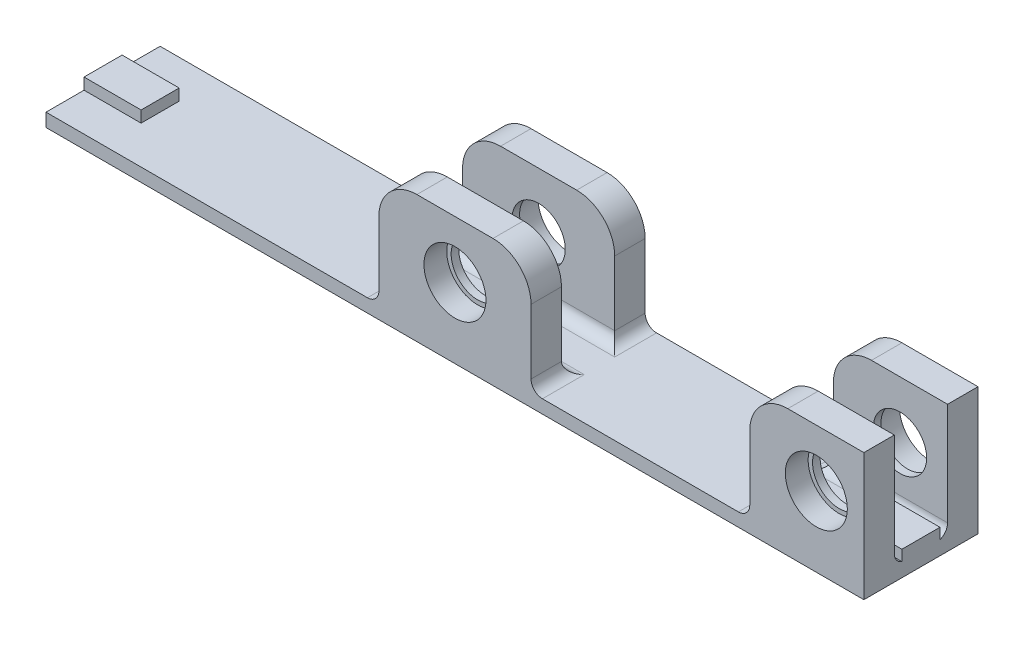
SolidWorks part; units mm, degrees
ref_plane "Front Plane" through (0, 0, 0) normal (0, 0, 1) x (1, 0, 0)
ref_plane "Top Plane" through (0, 0, 0) normal (0, 1, 0) x (1, 0, 0)
ref_plane "Right Plane" through (0, 0, 0) normal (1, 0, 0) x (0, 0, -1)
sketch "Sketch2" plane through (0, 0, 0) normal (0, 1, 0) x (1, 0, 0)
  line L1 (107.5, 15) -> (-107.5, 15)
  line L2 (107.5, 15) -> (107.5, -15)
  line L3 (107.5, -15) -> (-107.5, -15)
  line L4 (-107.5, 15) -> (-107.5, -15)
  line L5 (107.5, 15) -> (-107.5, -15) construction
  line L6 (107.5, -15) -> (-107.5, 15) construction
  point P0 (0, 0)
  dimension "D1" = 215
  dimension "D2" = 30
extrude "Boss-Extrude1" add sketch "Sketch2" along normal blind 3.5
sketch "HOLES TBD" plane through (0, 3.5, 0) normal (0, 1, 0) x (1, 0, 0)
  line L0 (100, 0) -> (-100, 0) construction
  circle A0 centre (-100, 0) radius 1.65
  circle A1 centre (100, 0) radius 1.65
  point P4 (0, 0)
  dimension "D2" = 3.3
  dimension "D1" = 200
sketch "Sketch4" plane through (0, 3.5, 0) normal (0, 1, 0) x (1, 0, 0)
  line L0 (-107.5, -15) -> (107.5, -15) construction
  line L1 (107.5, -15) -> (77.5, -15)
  line L2 (107.5, -15) -> (107.5, -7)
  line L3 (107.5, -7) -> (77.5, -7)
  line L4 (77.5, -15) -> (77.5, -7)
  line L5 (107.5, -15) -> (77.5, -7) construction
  line L6 (107.5, -7) -> (77.5, -15) construction
  line L7 (-20, -15) -> (20, -15)
  line L8 (-20, -15) -> (-20, -7)
  line L9 (-20, -7) -> (20, -7)
  line L10 (20, -15) -> (20, -7)
  line L11 (-20, -15) -> (20, -7) construction
  line L12 (-20, -7) -> (20, -15) construction
  line L13 (0, 0) -> (0, -15) construction
  line L14 (-100, 0) -> (100, 0) construction
  line L15 (-20, 7) -> (20, 15) construction
  line L16 (-20, 15) -> (20, 7) construction
  line L17 (107.5, 7) -> (77.5, 15) construction
  line L18 (107.5, 15) -> (77.5, 7) construction
  line L19 (20, 15) -> (20, 7)
  line L20 (-20, 7) -> (20, 7)
  line L21 (-20, 15) -> (-20, 7)
  line L22 (-20, 15) -> (20, 15)
  line L23 (77.5, 15) -> (77.5, 7)
  line L24 (107.5, 7) -> (77.5, 7)
  line L25 (107.5, 15) -> (107.5, 7)
  line L26 (107.5, 15) -> (77.5, 15)
  point P4 (92.5, -11)
  point P10 (0, -11)
  point P28 (0, 11)
  point P29 (92.5, 11)
  dimension "D1" = 8
  dimension "D2" = 30
  dimension "D3" = 40
extrude "Boss-Extrude2" add sketch "Sketch4" along normal blind 30
sketch "Sketch5" plane through (0, 0, 15) normal (0, 0, 1) x (1, 0, 0)
  line L0 (0, 3.5) -> (0, 18.5) construction
  line L3 (0, 18.5) -> (95, 18.5) construction
  line L6 (20, 33.5) -> (20, 3.5) construction
  circle A0 centre (0, 18.5) radius 8.15
  circle A1 centre (95, 18.5) radius 8.15
  point P10 (20, 18.5)
  dimension "D2" = 16.3
  dimension "D3" = 95
extrude "Bearing holes" cut sketch "Sketch5" against normal blind 6
mirror "Mirror1" about plane through (0, 0, 0) normal (0, 0, 1) of "Bearing holes"
sketch "Sketch7" plane through (0, 0, 9) normal (0, 0, 1) x (1, 0, 0)
  circle A0 centre (0, 18.5) radius 7
  circle A1 centre (95, 18.5) radius 7
  dimension "D1" = 14
extrude "Cut-Extrude2" cut sketch "Sketch7" against normal through all
chamfer "Chamfer1" [suppressed] distance 5 angle 45
fillet "Fillet1" radius 10 6 edges at (-20, 33.5, 11) (-20, 33.5, -11) (20, 33.5, -11) (20, 33.5, 11) (77.5, 33.5, 11) (77.5, 33.5, -11)
extrude "Cut-Extrude1" cut sketch "HOLES TBD" against normal through all
sketch "Sketch6" plane through (0, 3.5, 0) normal (0, 1, 0) x (1, 0, 0)
  line L5 (-107.5, 0) -> (107.5, 0) construction
  line L6 (107.5, -7) -> (107.5, 7) construction
  line L7 (-107.5, 15) -> (-107.5, -15) construction
  line L8 (0, 0) -> (0, 7.2837) construction
  line L9 (-107.5, 5) -> (-92.5, 5)
  line L10 (-107.5, 5) -> (-107.5, -5)
  line L11 (-107.5, -5) -> (-92.5, -5)
  line L12 (-92.5, 5) -> (-92.5, -5)
  line L13 (107.5, -5) -> (92.5, -5)
  line L14 (92.5, 5) -> (92.5, -5)
  line L15 (107.5, 5) -> (92.5, 5)
  line L16 (107.5, 5) -> (107.5, -5)
  point P3 (-107.5, 0)
  point P11 (-92.5, 0)
  dimension "D1" = 10
  dimension "D2" = 15
extrude "Boss-Extrude3" add sketch "Sketch6" along normal blind 3
fillet "Fillet2" radius 3 10 edges at (77.5, 3.5, 11) (92.5, 3.5, 7) (92.5, 3.5, -7) (77.5, 3.5, -11) (20, 3.5, 11) (20, 3.5, -11) (-20, 3.5, 11) (-20, 3.5, -11) (0, 3.5, 7) (0, 3.5, -7)
